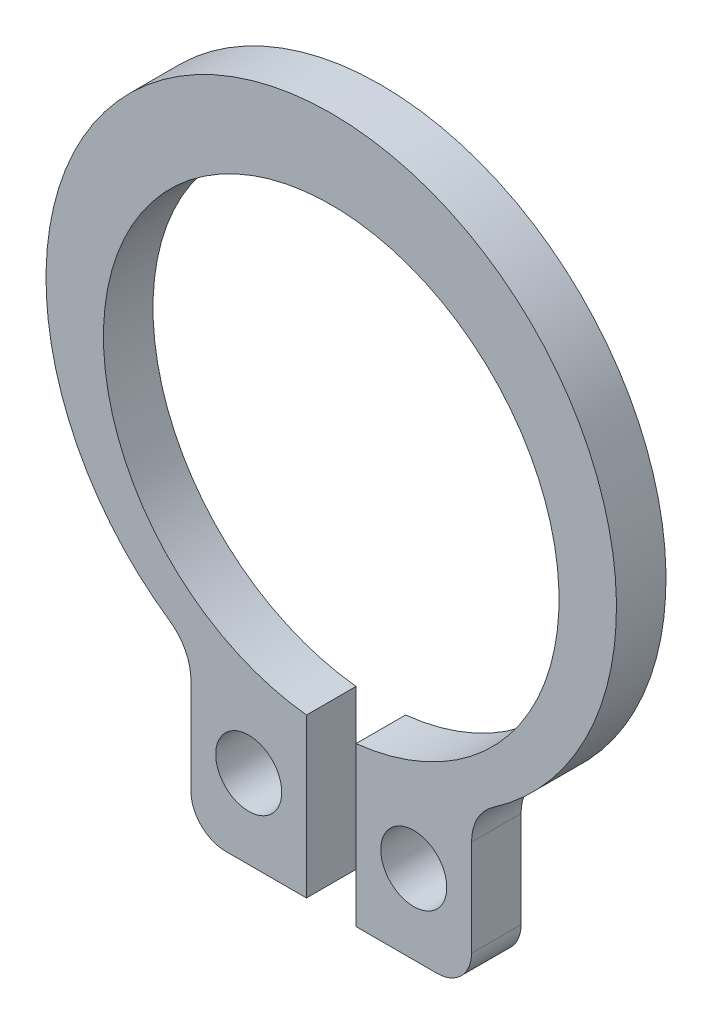
SolidWorks part; units mm, degrees
ref_plane "Front Plane" through (0, 0, 0) normal (0, 0, 1) x (1, 0, 0)
ref_plane "Top Plane" through (0, 0, 0) normal (0, 1, 0) x (1, 0, 0)
ref_plane "Right Plane" through (0, 0, 0) normal (1, 0, 0) x (0, 0, -1)
sketch "BodySke" plane through (0, 0, 0) normal (0, 0, 1) x (1, 0, 0)
  line L0 (0, 0) -> (0, 21.0564) construction
  line L1 (0, 0) -> (0, -11.0385) construction
  line L2 (-0.75, -6.8591) -> (-0.75, -11.6591)
  line L3 (-0.75, -11.6591) -> (-4.25, -11.6591)
  line L4 (-4.25, -11.6591) -> (-4.25, -6.8624)
  line L5 (4.25, -9.2608) -> (3.9811, -9.2608) construction
  line L7 (0.75, -11.6591) -> (4.25, -11.6591)
  line L8 (0.75, -6.8591) -> (0.75, -11.6591)
  line L9 (4.25, -11.6591) -> (4.25, -6.8624)
  arc A0 (0.75, -6.8591) -> (-0.75, -6.8591) centre (0, 0) ccw
  circle A2 centre (-2.5, -9.2608) radius 1
  circle A3 centre (2.5, -9.2608) radius 1
  arc A4 (4.25, -6.8624) -> (-4.25, -6.8624) centre (0, 0.66) ccw
  dimension "D3" = 8.64
  dimension "Groove_Depth" = 2.4
  dimension "D1" = 0.75
  dimension "D2" = 0.75
  dimension "Thickness" = 1.5
extrude "BaseBody" add sketch "BodySke" along normal blind 1.5
fillet "Fillet1" radius 1.5 2 edges at (4.25, -6.8624, 0.75) (-4.25, -6.8624, 0.75)
fillet "Fillet2" radius 1.05 2 edges at (4.25, -11.6591, 0.75) (-4.25, -11.6591, 0.75)
equation "\"D1@BodySke\" = \"Thickness@BodySke\" / 2"
equation "\"D2@BodySke\" = \"Thickness@BodySke\" / 2"
equation "\"D3@BodySke\" =  ( \"Groove_Diameter@BodySke\" + 1.45 * \"Groove_Depth@BodySke\" )  / 2"
equation "\"Thickness@BaseBody\" = \"Thickness@BodySke\""
equation "\"D1@Fillet1\" = \"Thickness@BodySke\""
equation "\"D1@Fillet2\" = \"Thickness@BodySke\" * 0.7"
